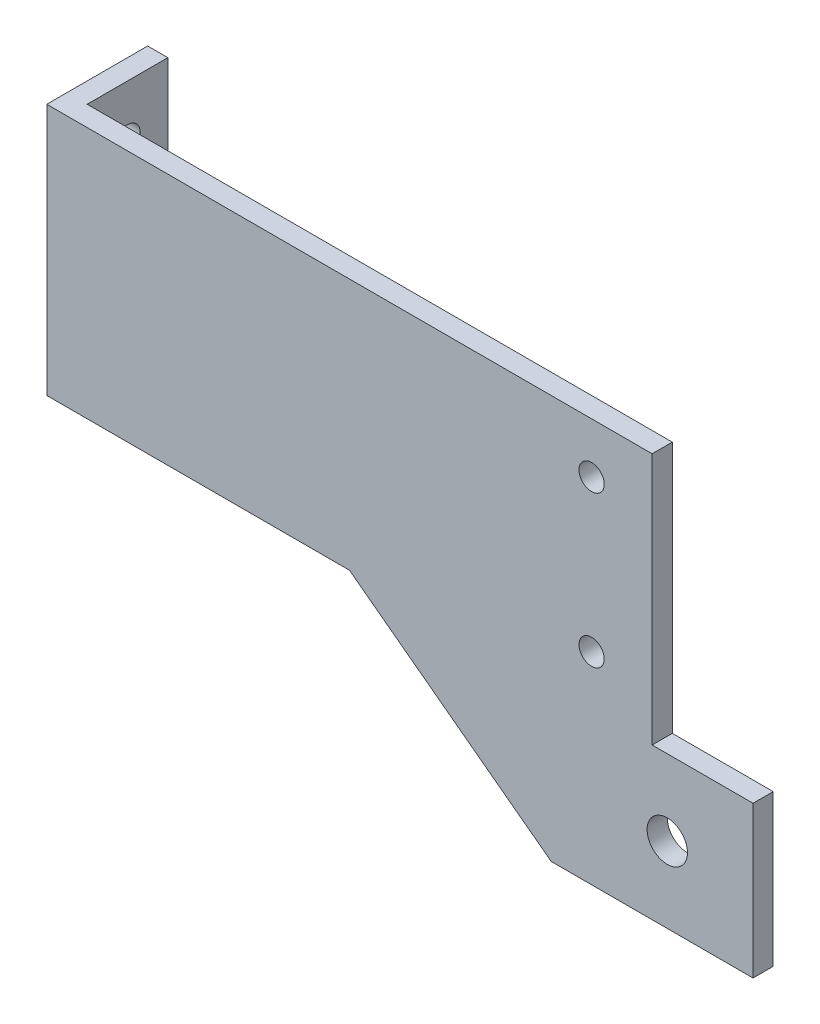
SolidWorks part; units mm, degrees
ref_plane "Спереди" through (0, 0, 0) normal (0, 0, 1) x (1, 0, 0)
ref_plane "Сверху" through (0, 0, 0) normal (0, 1, 0) x (1, 0, 0)
ref_plane "Справа" through (0, 0, 0) normal (1, 0, 0) x (0, 0, -1)
sketch "Эскиз1" plane through (0, 0, 0) normal (0, 1, 0) x (1, 0, 0)
  line L1 (0, 0) -> (140, 0)
  line L2 (0, 0) -> (0, 4)
  line L3 (4, 4) -> (140, 4)
  line L4 (140, 0) -> (140, 4)
  line L6 (0, 4) -> (0, 20)
  line L7 (0, 20) -> (4, 20)
  line L8 (4, 4) -> (4, 20)
  dimension "D1" = 140
  dimension "D2" = 4
  dimension "D3" = 20
  dimension "D4" = 4
extrude "Бобышка-Вытянуть1" add sketch "Эскиз1" along normal blind 80
sketch "Эскиз2" plane through (0, 0, 0) normal (-1, 0, 0) x (0, 0, 1)
  line L0 (-12, 44.9311) -> (-12, 11.555) construction
  line L1 (-20, 80) -> (0, 80) construction
  line L3 (0, 80) -> (0, 0) construction
  circle A0 centre (-12, 70) radius 2.5
  circle A1 centre (-12, 40) radius 2.5
  dimension "D2" = 5
  dimension "D3" = 5
  dimension "D1" = 12
  dimension "D4" = 30
  dimension "D5" = 10
extrude "Вырез-Вытянуть1" cut sketch "Эскиз2" against normal blind 10
sketch "Эскиз3" plane through (0, 0, 0) normal (0, 0, 1) x (1, 0, 0)
  line L0 (108, 46.6766) -> (108, 6.7064) construction
  line L2 (0, 80) -> (0, 0) construction
  line L5 (0, 80) -> (140, 80) construction
  circle A0 centre (108, 70) radius 2.5
  circle A1 centre (108, 40) radius 2.5
  circle A2 centre (123, 15) radius 4
  dimension "D2" = 5
  dimension "D3" = 5
  dimension "D6" = 8
  dimension "D1" = 108
  dimension "D4" = 30
  dimension "D5" = 10
  dimension "D7" = 25
  dimension "D8" = 15
extrude "Вырез-Вытянуть2" cut sketch "Эскиз3" against normal blind 10
sketch "Эскиз4" plane through (0, 0, 0) normal (0, 0, 1) x (1, 0, 0)
  line L0 (0, 30) -> (60, 30)
  line L1 (0, 80) -> (0, 0) construction
  line L2 (60, 30) -> (100, 0)
  line L3 (0, 0) -> (140, 0) construction
  line L4 (100, 0) -> (0, 0)
  line L5 (0, 0) -> (0, 30)
  line L6 (0, 80) -> (140, 80) construction
  dimension "D1" = 60
  dimension "D2" = 40
  dimension "D3" = 50
extrude "Вырез-Вытянуть3" cut sketch "Эскиз4" against normal blind 30
sketch "Эскиз6" plane through (0, 0, 0) normal (0, 0, 1) x (1, 0, 0)
  line L0 (120, 80) -> (120, 30)
  line L1 (0, 80) -> (140, 80) construction
  line L2 (120, 30) -> (140, 30)
  line L3 (140, 80) -> (140, 0) construction
  line L4 (140, 30) -> (140, 80)
  line L5 (140, 80) -> (120, 80)
  line L6 (0, 80) -> (0, 30) construction
  dimension "D1" = 120
  dimension "D2" = 50
extrude "Вырез-Вытянуть4" cut sketch "Эскиз6" against normal blind 10
